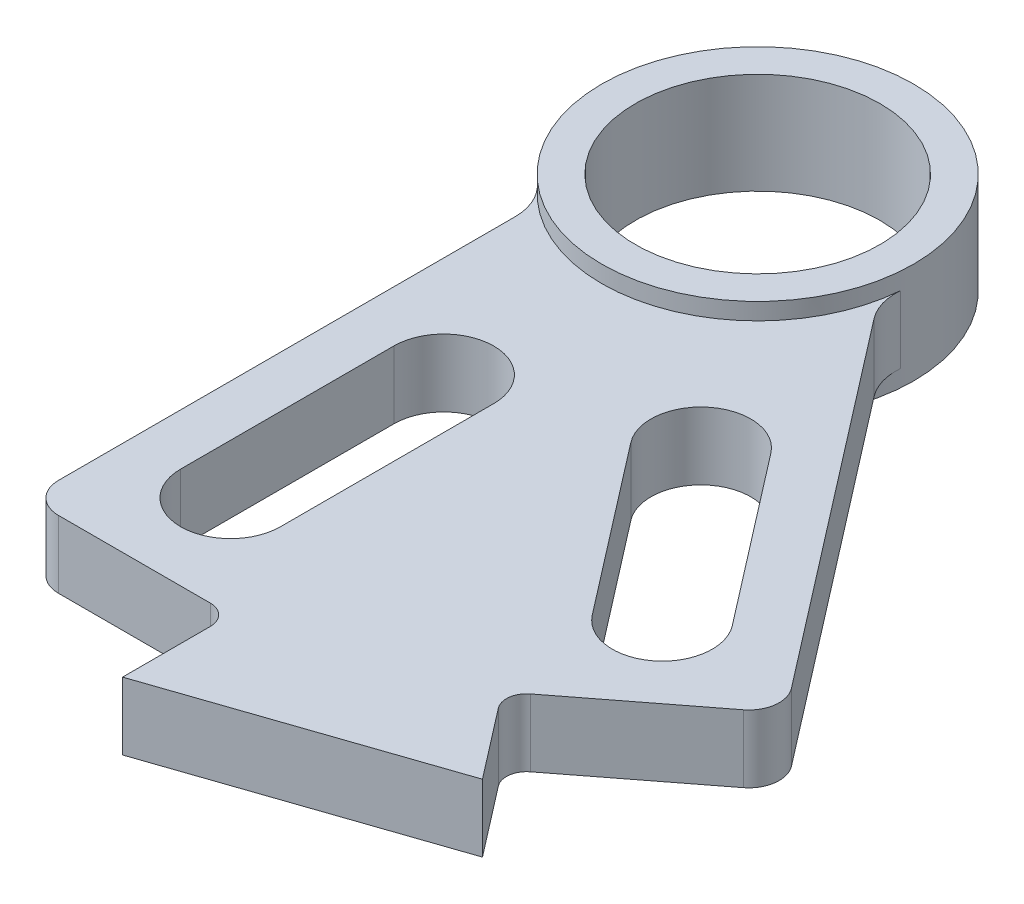
SolidWorks part; units mm, degrees
material "AISI 4130 Steel, normalized at 870C"
ref_plane "Front Plane" through (0, 0, 0) normal (0, 0, 1) x (1, 0, 0)
ref_plane "Top Plane" through (0, 0, 0) normal (0, 1, 0) x (1, 0, 0)
ref_plane "Right Plane" through (0, 0, 0) normal (1, 0, 0) x (0, 0, -1)
sketch "Sketch1" plane through (0, 0, 0) normal (0, 1, 0) x (1, 0, 0)
  line L0 (0, -54.3052) -> (0, -14.6812) construction
  line L1 (33.1693, -42.9983) -> (8.9672, -11.6244) construction
  line L2 (0, -49.6062) -> (0, -29.5402) construction
  line L5 (-4.699, -49.6062) -> (-4.699, -29.5402)
  line L8 (-9.525, -59.1312) -> (9.525, -59.1312)
  line L9 (28.5752, -52.6373) -> (43.6588, -41.0016)
  line L10 (-9.525, -59.1312) -> (-9.525, -11.1719)
  line L11 (43.6588, -41.0016) -> (14.3655, -3.028)
  line L12 (9.525, -59.1312) -> (9.525, -69.2912)
  line L13 (28.5752, -52.6373) -> (34.7809, -60.6818)
  line L14 (9.525, -69.2912) -> (34.7809, -60.6818)
  line L15 (0, -14.6812) -> (0, 0) construction
  line L16 (0, -59.1312) -> (0, -54.3052) construction
  line L17 (36.117, -46.8195) -> (33.1693, -42.9983)
  line L18 (4.699, -49.6062) -> (4.699, -29.5402)
  line L19 (18.043, -23.3896) -> (30.2992, -39.2777) construction
  line L20 (21.7636, -20.5195) -> (34.0198, -36.4075)
  line L21 (14.3224, -26.2597) -> (26.5786, -42.1478)
  line L22 (8.9672, -11.6244) -> (0, 0) construction
  line L23 (0, 0) -> (17.6201, -51.6893) construction
  line L25 (198.9203, -257.8659) -> (17.0668, -22.1241) construction
  line L27 (0, 0) -> (22.1529, -64.9865) construction
  circle A0 centre (0, 0) radius 11.5062
  circle A1 centre (0, 0) radius 14.6812
  arc A2 (-4.699, -49.6062) -> (4.699, -49.6062) centre (0, -49.6062) ccw
  arc A3 (4.699, -29.5402) -> (-4.699, -29.5402) centre (0, -29.5402) ccw
  arc A4 (21.7636, -20.5195) -> (14.3224, -26.2597) centre (18.043, -23.3896) ccw
  arc A5 (26.5786, -42.1478) -> (34.0198, -36.4075) centre (30.2992, -39.2777) ccw
  point P9 (0, -39.5732)
  point P14 (24.1711, -31.3336)
  point P23 (0, -59.1312)
  point P26 (36.117, -46.8195)
  point P33 (0, -54.3052)
  point P36 (33.1693, -42.9983)
  point P38 (0, -24.8412)
  dimension "D2" = 29.3624
  dimension "D3" = 44.45
  dimension "D4" = 4.826
  dimension "D6" = 10.16
  dimension "D5" = 4.826
  dimension "D8" = 10.16
  dimension "D9" = 54.61
  dimension "D7" = 19.05
extrude "Bearing extrude" add sketch "Sketch1" along normal mid plane 9.525 contours A1 A0 region at (-5.9782, 0, -12.9529)
extrude "Boss-Extrude2" add sketch "Sketch1<5>" along normal mid plane 6.35 contours A1 L10 L8 L12 L14 L13 L9 L11 A4 A2 region at (13.1687, 0, 38.6309)
sketch "Sketch1<5>" plane through (0, 0, 0) normal (0, 1, 0) x (1, 0, 0) same geometry as "Sketch1"
sketch3d "Tab Point"
  line L0 (17.6201, 0, 51.6893) -> (17.6201, 22.225, 51.6893) construction
  line L1 (0, 0, 0) -> (17.6201, 0, 51.6893) construction
  line L2 (0, 0, 0) -> (22.1529, 0, 64.9865) construction
  dimension "D1" = 22.225
fillet "Fillet1" radius 5.08 2 edges at (14.3655, 0, 3.028) (-9.525, 0, 11.1719)
fillet "Fillet2" radius 1.905 2 edges at (28.5752, 0, 52.6373) (9.525, 0, 59.1312)
fillet "Fillet3" radius 2.8575 2 edges at (43.6588, 0, 41.0016) (-9.525, 0, 59.1312)
equation "\"Apex_thickness\"= .25"
equation "\"Bearing_diameter\"= .906"
equation "\"A-arm_angle\"= 32.91"
equation "\"D1@Sketch1\"=\"Bearing_diameter\""
equation "\"D1@Boss-Extrude2\"= \"Apex_thickness\""
equation "\"apex slot\"= 1.4"
equation "\"tube diameter\"= 5 / 8"
